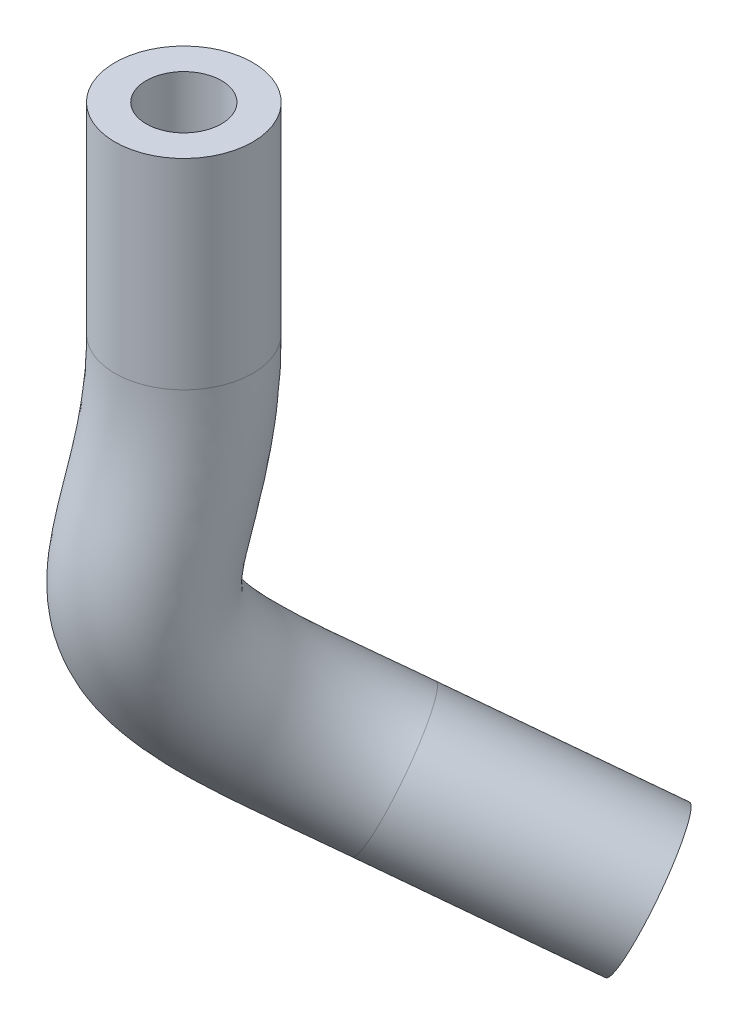
SolidWorks part; units mm, degrees
material "Silicon Rubber"
ref_plane "X-Y Datum" through (0, 0, 0) normal (0, 0, 1) x (1, 0, 0)
ref_plane "X-Z Datum" through (0, 0, 0) normal (0, 1, 0) x (1, 0, 0)
ref_plane "Y-Z Datum" through (0, 0, 0) normal (1, 0, 0) x (0, 0, -1)
sketch3d "3DSketch1"
  line L0 (237.8668, 107.6153, -14.6249) -> (219.2795, 118.3793, -1.0673)
  line L1 (208.2074, 175.7084, 14.5039) -> (208.2074, 168.4084, 14.5039) construction
  line L2 (208.2074, 168.4084, 14.5039) -> (208.2074, 193.8084, 14.5039)
  line L6 (208.2074, 175.7084, 14.5039) -> (208.2074, 168.4084, 14.5039) construction
  line L10 (208.2074, 175.7084, 14.5039) -> (208.2074, 168.4084, 14.5039) construction
  line L14 (208.2074, 175.7084, 14.5039) -> (208.2074, 168.4084, 14.5039) construction
  line L18 (223.9263, 115.6883, -4.4567) -> (237.8668, 107.6153, -14.6249) construction
  circle A0 centre (223.9263, 115.6883, -4.4567) radius 3.175 construction
  circle A1 centre (237.8668, 107.6153, -14.6249) radius 4.7625 construction
  circle A2 centre (223.9263, 115.6883, -4.4567) radius 3.175 construction
  circle A3 centre (237.8668, 107.6153, -14.6249) radius 4.7625 construction
  spline S0 degree 3 poles (208.2074, 168.4084, 14.5039) (208.2074, 154.3812, 14.5039) (205.2541, 138.9118, 24.6365) (208.3103, 124.7316, 6.9335) (219.2795, 118.3793, -1.0673) knots 0 0 0 0 0.453923 1 1 1 1
  point P3 (77.5727, 90.6233, 155.9968)
  point P15 (0, 0, 0)
  point P18 (221.6029, 117.0338, -2.762)
  point P21 (241.3519, 105.5971, -17.1669)
  point P23 (221.6029, 117.0338, -2.762)
  point P25 (241.3519, 105.5971, -17.1669)
  point P26 (0, 0, 0)
  dimension "D1" = 25.4
  dimension "D2" = 25.4
sweep "Sweep1" add path "3DSketch1" circular profile diameter 17.4625 parameters "D3"=17.4625
sweep "Cut-Sweep1" cut path "3DSketch1<2>" circular profile diameter 9.525 parameters "D3"=9.525
sketch3d "3DSketch1<2>" same geometry as "3DSketch1"
sketch3d "3DSketch3"
  circle A1 centre (219.2795, 118.3793, -1.0673) radius 8.7313 construction
  circle A2 centre (208.2074, 168.4084, 14.5039) radius 8.7312 construction
  circle A4 centre (219.2795, 118.3793, -1.0673) radius 8.7313 construction
  circle A5 centre (208.2074, 168.4084, 14.5039) radius 8.7312 construction
  point P2 (225.6689, 114.6792, -5.7277)
  point P5 (208.2074, 159.6772, 14.5039)
  point P7 (225.6689, 114.6792, -5.7277)
  point P9 (208.2074, 159.6772, 14.5039)
